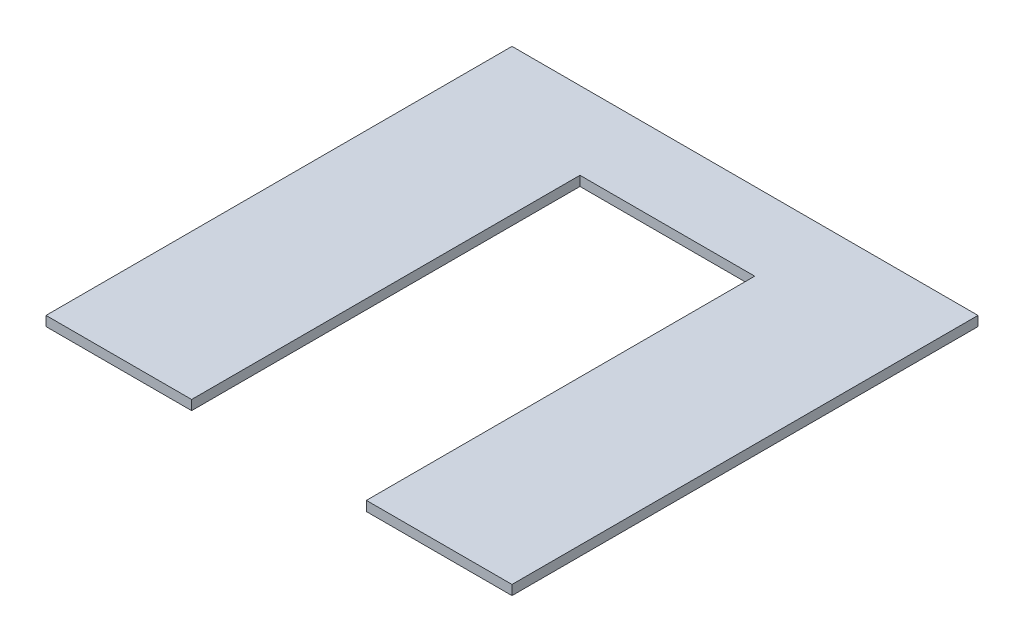
SolidWorks part; units mm, degrees
ref_plane "Front Plane" through (0, 0, 0) normal (0, 0, 1) x (1, 0, 0)
ref_plane "Top Plane" through (0, 0, 0) normal (0, 1, 0) x (1, 0, 0)
ref_plane "Right Plane" through (0, 0, 0) normal (1, 0, 0) x (0, 0, -1)
sketch "Sketch1" plane through (0, 0, 0) normal (0, 1, 0) x (1, 0, 0)
  line L0 (0, -55) -> (0, 55) construction
  line L1 (-152.4, -25.4) -> (152.4, -25.4)
  line L2 (-152.4, -25.4) -> (-152.4, 25.4)
  line L3 (-152.4, 25.4) -> (152.4, 25.4)
  line L4 (152.4, -25.4) -> (152.4, 25.4)
  line L5 (-152.4, -25.4) -> (152.4, 25.4) construction
  line L6 (-152.4, 25.4) -> (152.4, -25.4) construction
  line L7 (-152.4, -25.4) -> (-50.8, -25.4)
  line L8 (-152.4, -25.4) -> (-152.4, -279.4)
  line L9 (-152.4, -279.4) -> (-50.8, -279.4)
  line L10 (-50.8, -25.4) -> (-50.8, -279.4)
  line L11 (50.8, -25.4) -> (50.8, -279.4)
  line L12 (152.4, -279.4) -> (50.8, -279.4)
  line L13 (152.4, -25.4) -> (152.4, -279.4)
  line L14 (152.4, -25.4) -> (50.8, -25.4)
  line L15 (-57.15, -25.4) -> (-57.15, -279.4)
  line L16 (57.15, -25.4) -> (57.15, -279.4)
  point P0 (0, 0)
  dimension "D1" = 304.8
  dimension "D2" = 50.8
  dimension "D3" = 304.8
  dimension "D4" = 101.6
  dimension "D5" = 6.35
extrude "Boss-Extrude1" add sketch "Sketch1" along normal blind 6.35 contours L15 L1 L8 L9 | L14 L16 L12 L13 | L1 L7 L14 L4 L3 L2 region at (0, 0, 0) region at (-104.775, 0, 152.4) region at (104.775, 0, 152.4)
